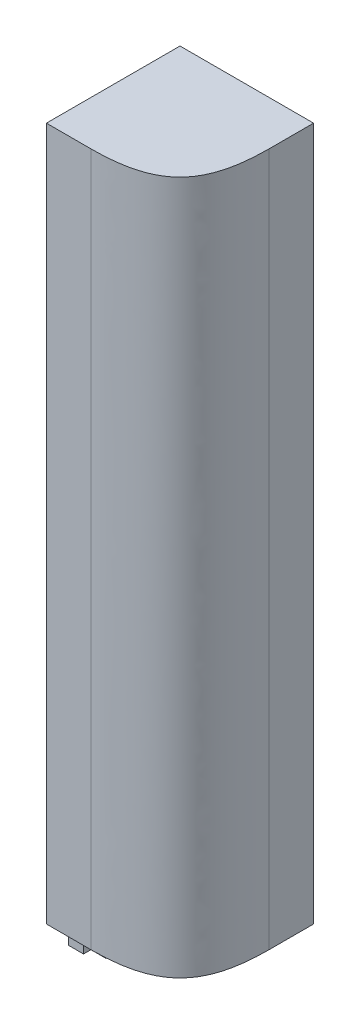
SolidWorks part; units mm, degrees
ref_plane "Front Plane" through (0, 0, 0) normal (0, 0, 1) x (1, 0, 0)
ref_plane "Top Plane" through (0, 0, 0) normal (0, 1, 0) x (1, 0, 0)
ref_plane "Right Plane" through (0, 0, 0) normal (1, 0, 0) x (0, 0, -1)
sketch "Sketch1" plane through (0, 0, 0) normal (0, 1, 0) x (1, 0, 0)
  line L1 (0, 0) -> (36, 0)
  line L2 (0, 0) -> (0, 36)
  line L3 (0, 36) -> (36, 36)
  line L4 (36, 0) -> (36, 36)
  dimension "D1" = 36
  dimension "D2" = 36
extrude "Boss-Extrude1" add sketch "Sketch1" along normal blind 186.9
fillet "Fillet1" radius 24 1 edges at (36, 93.45, 0) conic rho 0.55
sketch "Sketch2" plane through (0, 0, 0) normal (0, -1, 0) x (1, 0, 0)
  line L0 (36, -24) -> (36, -36) construction
  line L1 (0, -12.5) -> (14.28, -12.5)
  line L2 (0, -12.5) -> (0, -36)
  line L3 (0, -36) -> (14.28, -36)
  line L4 (14.28, -12.5) -> (14.28, -36)
  line L5 (0, 0) -> (12, 0) construction
  line L6 (0, -36) -> (0, 0) construction
  line L7 (36, -36) -> (0, -36) construction
  dimension "D1" = 21.72
  dimension "D2" = 12.5
  dimension "D3" = 0
  dimension "D4" = 0
extrude "Cut-Extrude1" cut sketch "Sketch2" against normal blind 27
sketch "Sketch3" plane through (0, 27, 0) normal (0, -1, 0) x (1, 0, 0)
  line L0 (0, -12.5) -> (0, -36) construction
  line L1 (0, -15) -> (11.78, -15)
  line L2 (0, -15) -> (0, -36)
  line L3 (0, -36) -> (11.78, -36)
  line L4 (11.78, -15) -> (11.78, -36)
  line L5 (0, -36) -> (14.28, -36) construction
  line L6 (14.28, -12.5) -> (0, -12.5) construction
  line L7 (14.28, -36) -> (14.28, -12.5) construction
  dimension "D1" = 2.5
  dimension "D2" = 2.5
extrude "Cut-Extrude2" cut sketch "Sketch3" against normal blind 8
sketch "Sketch4" plane through (0, 0, 0) normal (0, -1, 0) x (1, 0, 0)
  line L0 (36, -24) -> (36, -36) construction
  line L1 (0, 0) -> (12, 0) construction
  circle A0 centre (21, -15) radius 2
  point P6 (12.232, -0.0004)
  dimension "D1" = 4
  dimension "D2" = 15
  dimension "D3" = 15
extrude "Cut-Extrude3" cut sketch "Sketch4" against normal blind 5
sketch "Sketch5" plane through (0, 0, 0) normal (0, -1, 0) x (1, 0, 0)
  line L0 (36, -24) -> (36, -36) construction
  line L1 (18.28, -28) -> (22.28, -28)
  line L2 (18.28, -28) -> (18.28, -32)
  line L3 (18.28, -32) -> (32, -32)
  line L4 (32, -28) -> (32, -32)
  line L5 (36, -36) -> (14.28, -36) construction
  line L6 (14.28, -36) -> (14.28, -12.5) construction
  line L7 (0, 0) -> (12, 0) construction
  line L8 (4, -2) -> (8, -2)
  line L9 (4, -2) -> (4, -10.5)
  line L10 (4, -10.5) -> (8, -10.5)
  line L11 (8, -2) -> (8, -4)
  line L12 (14.28, -12.5) -> (0, -12.5) construction
  line L13 (0, -12.5) -> (0, 0) construction
  line L14 (8, -8.5) -> (8, -10.5)
  line L15 (8, -4) -> (12, -4)
  line L17 (8, -8.5) -> (12, -8.5)
  line L18 (12, -4) -> (12, -8.5)
  line L20 (22.28, -28) -> (22.28, -24)
  line L21 (22.28, -24) -> (28, -24)
  line L22 (28, -28) -> (28, -24)
  line L23 (28, -28) -> (32, -28)
  dimension "D1" = 4
  dimension "D2" = 4
  dimension "D3" = 4
  dimension "D4" = 4
  dimension "D5" = 2
  dimension "D6" = 2
  dimension "D7" = 4
  dimension "D8" = 4
  dimension "D9" = 2
  dimension "D10" = 2
  dimension "D11" = 4
  dimension "D12" = 4
  dimension "D13" = 4
  dimension "D14" = 4
  dimension "D15" = 24
  dimension "D16" = 24
extrude "Boss-Extrude2" add sketch "Sketch5" along normal blind 4
